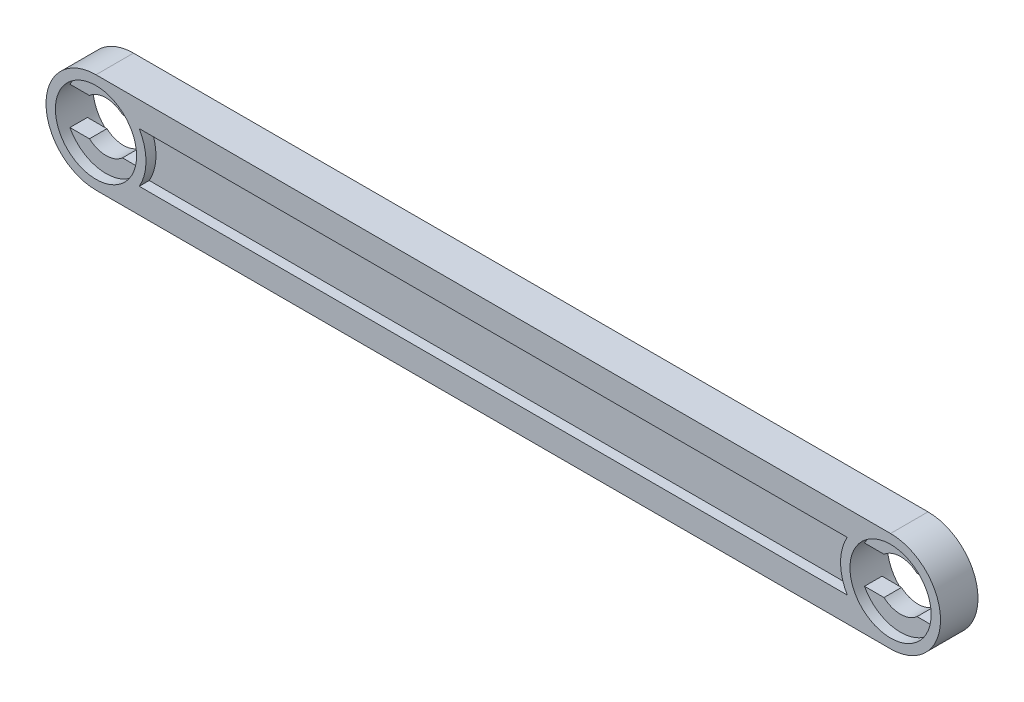
SolidWorks part; units mm, degrees
ref_plane "前视基准面" through (0, 0, 0) normal (0, 0, 1) x (1, 0, 0)
ref_plane "上视基准面" through (0, 0, 0) normal (0, 1, 0) x (1, 0, 0)
ref_plane "右视基准面" through (0, 0, 0) normal (1, 0, 0) x (0, 0, -1)
sketch "草图1" plane through (0, 0, 0) normal (0, 0, 1) x (1, 0, 0)
  line L1 (0, 4) -> (63.6, 4)
  line L3 (0, -4) -> (63.6, -4)
  arc A0 (0, 4) -> (0, -4) centre (0, 0) ccw
  arc A1 (63.6, -4) -> (63.6, 4) centre (63.6, 0) ccw
  dimension "D1" = 63.6
  dimension "D2" = 4
  dimension "D4" = 4
  dimension "D3" = 63.6
extrude "凸台-拉伸1" add sketch "草图1" against normal blind 3
sketch "草图2" plane through (0, 0, 0) normal (0, 0, 1) x (1, 0, 0)
  line L0 (1.3229, -1.5) -> (2.8831, -1.5)
  line L1 (-2.8831, -1.5) -> (-1.3229, -1.5)
  line L2 (1.3229, 1.5) -> (2.8831, 1.5)
  line L3 (-2.8831, 1.5) -> (-1.3229, 1.5)
  arc A0 (1.3229, 1.5) -> (-1.3229, 1.5) centre (0, 0) ccw
  arc A1 (-2.8831, 1.5) -> (-2.8831, -1.5) centre (0, 0) ccw
  arc A3 (2.8831, -1.5) -> (2.8831, 1.5) centre (0, 0) ccw
  arc A4 (-1.3229, -1.5) -> (1.3229, -1.5) centre (0, 0) ccw
extrude "切除-拉伸1" cut sketch "草图2" against normal up to next
sketch "草图3" plane through (0, 0, 0) normal (0, 0, 1) x (1, 0, 0)
  circle A1 centre (0, 0) radius 3.25
extrude "切除-拉伸2" cut sketch "草图3" against normal blind 0.8
extrude "切除-拉伸3" cut sketch "草图3<2>" along normal blind 0.8 from offset 3 offset against normal yes
sketch "草图3<2>" plane through (0, 0, 0) normal (0, 0, 1) x (1, 0, 0) same geometry as "草图3"
pattern_linear "阵列(线性)1" count 2 spacing 63.6 along (1, 0, 0) of "切除-拉伸1", "切除-拉伸2", "切除-拉伸3"
sketch "草图4" plane through (0, 0, 0) normal (0, 0, 1) x (1, 0, 0)
  line L0 (0, 0) -> (0, 2) construction
  line L1 (0, 0) -> (0, -2) construction
  line L2 (0, 2) -> (3.4641, 2) construction
  line L3 (0, -2) -> (3.4641, -2) construction
  line L4 (63.6, 0) -> (63.6, 2) construction
  line L5 (63.6, 2) -> (60.1359, 2) construction
  line L6 (63.6, 0) -> (63.6, -2) construction
  line L7 (63.6, -2) -> (60.1359, -2) construction
  line L8 (3.4641, 2) -> (60.1359, 2)
  line L9 (3.4641, -2) -> (60.1359, -2)
  arc A0 (1.3229, 1.5) -> (-1.3229, 1.5) centre (0, 0) ccw construction
  arc A1 (-1.3229, -1.5) -> (1.3229, -1.5) centre (0, 0) ccw construction
  arc A2 (3.4641, -2) -> (3.4641, 2) centre (0, 0) ccw
  arc A3 (60.1359, 2) -> (60.1359, -2) centre (63.6, 0) ccw
  arc A4 (64.9229, 1.5) -> (62.2771, 1.5) centre (63.6, 0) ccw construction
  arc A5 (62.2771, -1.5) -> (64.9229, -1.5) centre (63.6, 0) ccw construction
extrude "切除-拉伸4" cut sketch "草图4" against normal blind 0.8
sketch "草图5" plane through (0, 0, -3) normal (0, 0, -1) x (-1, 0, 0)
  line L0 (-59.6, -2) -> (-59.6, 2)
  line L1 (-4, -2) -> (-4, 2)
  line L2 (-59.6, 2) -> (-4, 2)
  line L3 (-59.6, 0) -> (-4, 0) construction
  line L4 (-59.6, -2) -> (-4, -2)
  circle A0 centre (-63.6, 0) radius 4 construction
  circle A1 centre (0, 0) radius 4 construction
  dimension "D1" = 2
  dimension "D2" = 2
extrude "切除-拉伸5" cut sketch "草图5" against normal blind 0.8
